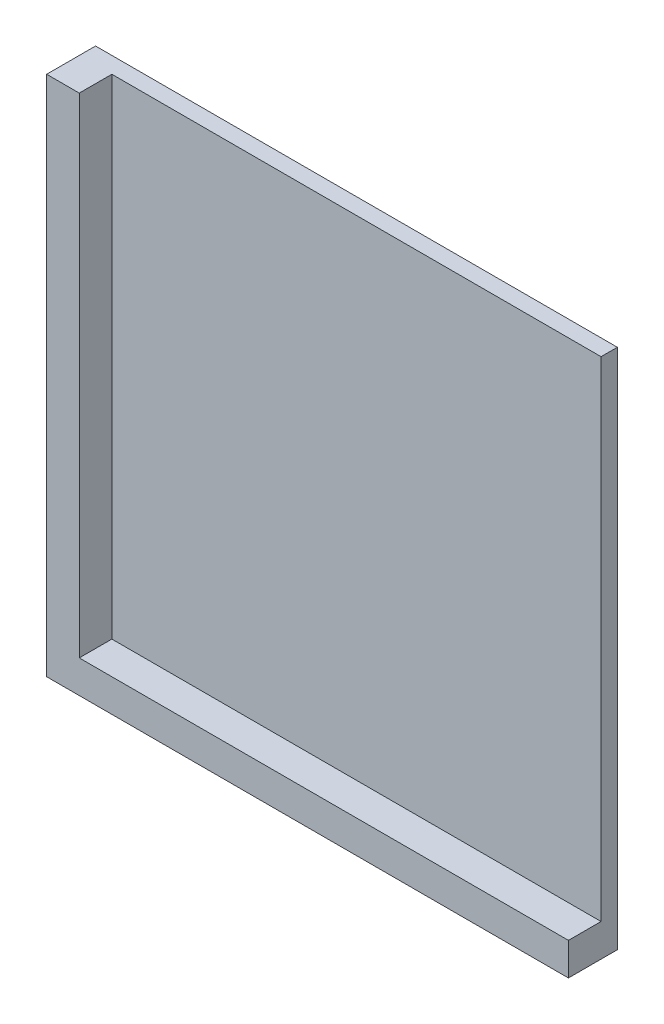
SolidWorks part; units mm, degrees
material "Cedar"
ref_plane "Front Plane" through (0, 0, 0) normal (0, 0, 1) x (1, 0, 0)
ref_plane "Top Plane" through (0, 0, 0) normal (0, 1, 0) x (1, 0, 0)
ref_plane "Right Plane" through (0, 0, 0) normal (1, 0, 0) x (0, 0, -1)
sketch "Sketch1" plane through (0, 0, 0) normal (0, 0, 1) x (1, 0, 0)
  line L0 (-177.8, 177.8) -> (-177.8, 203.2)
  line L1 (-177.8, -177.8) -> (177.8, -177.8)
  line L2 (-177.8, -177.8) -> (-177.8, 177.8)
  line L3 (-177.8, 177.8) -> (177.8, 177.8)
  line L4 (177.8, -177.8) -> (177.8, 177.8)
  line L5 (-177.8, -177.8) -> (177.8, 177.8) construction
  line L6 (-177.8, 177.8) -> (177.8, -177.8) construction
  line L7 (-203.2, 203.2) -> (203.2, 203.2)
  line L8 (-203.2, 203.2) -> (-203.2, -203.2)
  line L9 (-203.2, -203.2) -> (203.2, -203.2)
  line L10 (203.2, 203.2) -> (203.2, -203.2)
  line L11 (-203.2, 203.2) -> (203.2, -203.2) construction
  line L12 (-203.2, -203.2) -> (203.2, 203.2) construction
  line L13 (177.8, -177.8) -> (203.2, -177.8)
  point P0 (0, 0)
  point P6 (0, 0)
  point P11 (0, 0)
  dimension "D1" = 355.6
  dimension "D2" = 25.4
  dimension "D3" = 25.4
extrude "Boss-Extrude1" add sketch "Sketch1" along normal blind 25.4 contours L13 L1 L2 L0 L7 L8 L9 L10 region at (-183.5474, 0, 0)
extrude "Boss-Extrude2" add sketch "Sketch1<3>" against normal blind 12.7 contours L4 L13 L10 L7 L0 L3 | L1 L4 L3 L2 | L13 L1 L2 L0 L7 L8 L9 L10 region at (-183.5474, 0, 0) region at (0, 0, 0) region at (-172.4118, 190.5, 0)
sketch "Sketch1<3>" plane through (0, 0, 0) normal (0, 0, 1) x (1, 0, 0) same geometry as "Sketch1"
